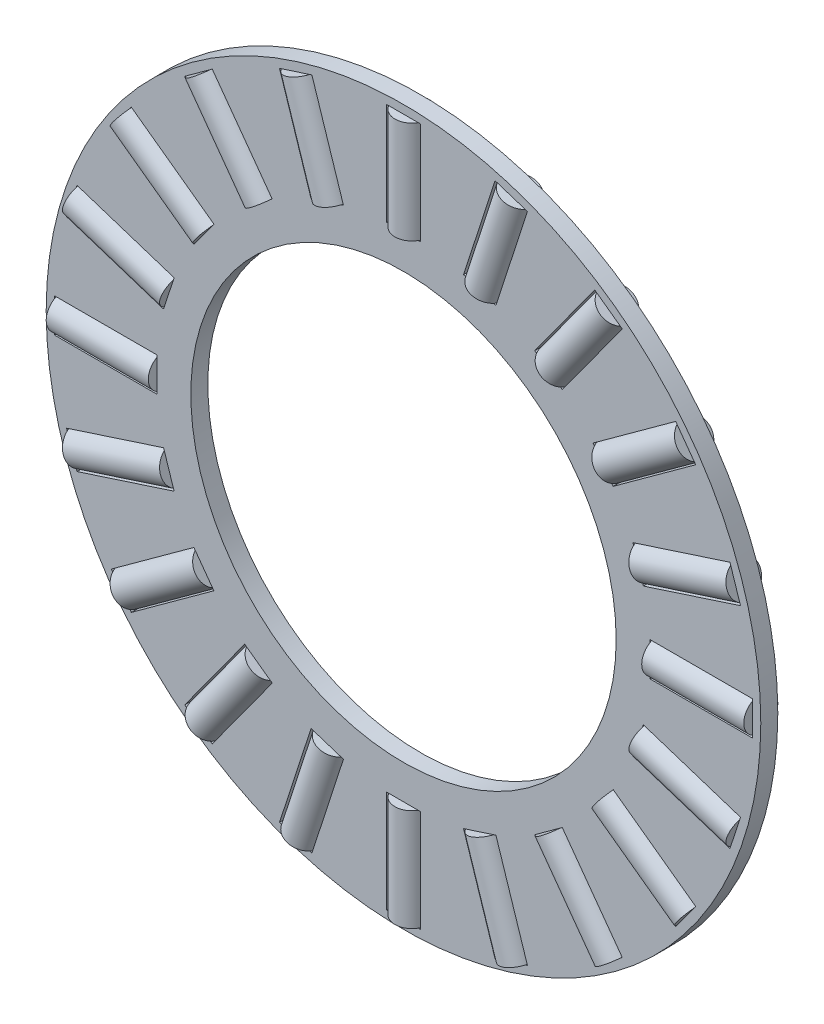
SolidWorks part; units mm, degrees
ref_plane "前视基准面" through (0, 0, 0) normal (0, 0, 1) x (1, 0, 0)
ref_plane "上视基准面" through (0, 0, 0) normal (0, 1, 0) x (1, 0, 0)
ref_plane "右视基准面" through (0, 0, 0) normal (1, 0, 0) x (0, 0, -1)
other "Configuration Table"
sketch "草图1" plane through (0, 0, 0) normal (0, 0, 1) x (1, 0, 0)
  circle A0 centre (0, 0) radius 21
  circle A1 centre (0, 0) radius 12.5
  dimension "D1" = 25
  dimension "D2" = 42
extrude "凸台-拉伸1" add sketch "草图1" along normal blind 1 contours A0 | A1
ref_plane "基准面1" through (0, 0, 0.5) normal (0, 0, 1) x (1, 0, 0)
sketch "草图3" plane through (0, 0, 0.5) normal (0, 0, 1) x (1, 0, 0)
  line L0 (0, 14.5) -> (1, 14.5)
  line L1 (0, -0.55) -> (0, 0.55) construction
  line L2 (1, 14.5) -> (1, 20.5)
  line L3 (1, 20.5) -> (-1, 20.5)
  line L4 (-1, 20.5) -> (-1, 14.5)
  line L5 (-1, 14.5) -> (0, 14.5)
  line L6 (0.55, 0) -> (-0.55, 0) construction
  line L7 (0, 21.9842) -> (0, 13.7018) construction
  dimension "D1" = 2
  dimension "D2" = 6
  dimension "D3" = 1
  dimension "D4" = 14.5
extrude "切除-拉伸1" cut sketch "草图3" against normal through all and the other way through all
pattern_circular "阵列(圆周)1" count 20 over 360 about axis through (0, 0, 1) along (0, 0, -1) of "切除-拉伸1"
ref_plane "基准面2" through (0, 20.5, 0) normal (0, 1, 0) x (1, 0, 0)
sketch "草图5" plane through (0, 20.5, 0) normal (0, 1, 0) x (1, 0, 0)
  line L0 (-23.1, -0.5) -> (23.1, -0.5) construction
  line L1 (0, -0.55) -> (0, 0.55) construction
  circle A0 centre (0, -0.5) radius 1
  point P6 (0, -0.5)
  dimension "D1" = 2
extrude "凸台-拉伸5" add sketch "草图5" against normal up to surface (6 mm away) separate body up to face at (0, 14.5, 0.5)
pattern_circular "阵列(圆周)8" count 20 over 360 about axis through (0, 0, 1) along (0, 0, -1) reverse direction yes of bodies 110
